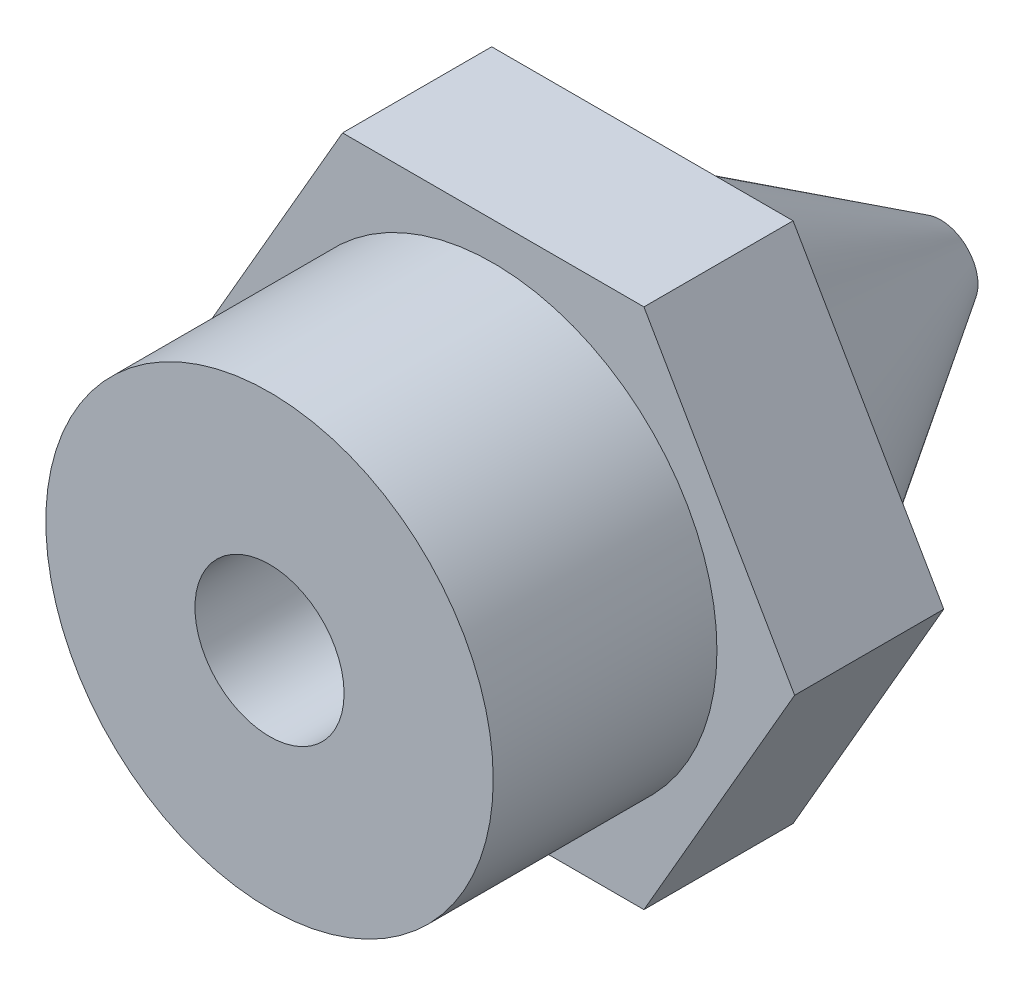
SolidWorks part; units mm, degrees
ref_plane "Plan de face" through (0, 0, 0) normal (0, 0, 1) x (1, 0, 0)
ref_plane "Plan de dessus" through (0, 0, 0) normal (0, 1, 0) x (1, 0, 0)
ref_plane "Plan de droite" through (0, 0, 0) normal (1, 0, 0) x (0, 0, -1)
sketch "Esquisse1" plane through (0, 0, 0) normal (0, 0, 1) x (1, 0, 0)
  line L1 (4.0415, 0) -> (2.0207, 3.5)
  line L2 (2.0207, 3.5) -> (-2.0207, 3.5)
  line L3 (-2.0207, 3.5) -> (-4.0415, 0)
  line L4 (-4.0415, 0) -> (-2.0207, -3.5)
  line L5 (-2.0207, -3.5) -> (2.0207, -3.5)
  line L6 (2.0207, -3.5) -> (4.0415, 0)
  circle A0 centre (0, 0) radius 3.5 construction
  dimension "D1" = 7
extrude "Boss.-Extru.1" add sketch "Esquisse1" along normal blind 9 contours L3 L4 L5 L6 L1 L2
sketch "Esquisse2" plane through (0, 0, 9) normal (0, 0, 1) x (1, 0, 0)
  line L1 (-9.4849, 6.2226) -> (10.1391, 6.2226)
  line L2 (-9.4849, 6.2226) -> (-9.4849, -9.3115)
  line L3 (-9.4849, -9.3115) -> (10.1391, -9.3115)
  line L4 (10.1391, 6.2226) -> (10.1391, -9.3115)
  circle A0 centre (0, 0) radius 3
  dimension "D1" = 6
extrude "Enlèv. mat.-Extru.1" cut sketch "Esquisse2" against normal blind 3
cosmetic thread "Représentation de filetage1" parameters "D1"=3, "D2"=4.891
sketch "Esquisse3" plane through (0, 0, 0) normal (0, 0, -1) x (-1, 0, 0)
  line L1 (5.6434, -6.9413) -> (-5.6238, -6.9413)
  line L2 (5.6434, -6.9413) -> (5.6434, 7.0198)
  line L3 (5.6434, 7.0198) -> (-5.6238, 7.0198)
  line L4 (-5.6238, -6.9413) -> (-5.6238, 7.0198)
  circle A0 centre (0, 0) radius 3
  dimension "D1" = 6
extrude "Enlèv. mat.-Extru.2" cut sketch "Esquisse3" against normal blind 4
chamfer "Chanfrein1" distance 4 angle 32 1 edges at (-3, 0, 0) first distance on face at (-3, 0, 4)
sketch "Esquisse4" plane through (0, 0, 0) normal (0, 1, 0) x (1, 0, 0)
  line L0 (0, -9.4046) -> (0, 0.4979) construction
  line L1 (0, -9) -> (1, -9)
  line L2 (-3, -9) -> (3, -9) construction
  line L3 (0, 0) -> (0.2, 0)
  line L4 (0.2, 0) -> (0.2, -0.5)
  line L5 (0.2, -0.5) -> (1, -1.6425)
  line L6 (1, -9) -> (1, -1.6425)
  line L7 (0, -9) -> (0, 0)
  dimension "D1" = 1
  dimension "D2" = 0.2
  dimension "D3" = 0.5
revolve "Enlèvement de matière-Révolution1" cut sketch "Esquisse4" angle 360 about L0
chamfer "Chanfrein2" [suppressed] distance 0.5 angle 45
